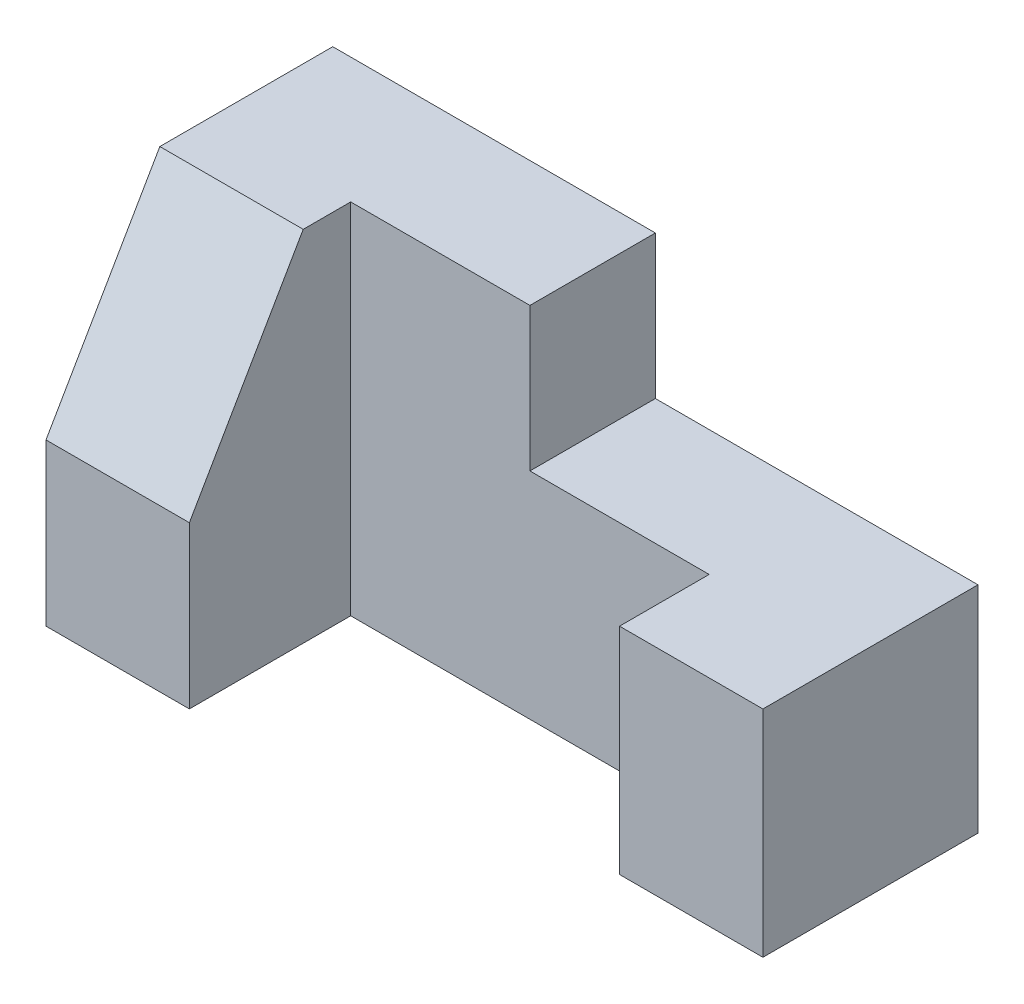
SolidWorks part; units mm, degrees
ref_plane "Front Plane" through (0, 0, 0) normal (0, 0, 1) x (1, 0, 0)
ref_plane "Top Plane" through (0, 0, 0) normal (0, 1, 0) x (1, 0, 0)
ref_plane "Right Plane" through (0, 0, 0) normal (1, 0, 0) x (0, 0, -1)
sketch "Sketch1" plane through (0, 0, 0) normal (0, 0, 1) x (1, 0, 0)
  line L0 (0, 0) -> (114.3, 0)
  line L1 (114.3, 0) -> (114.3, 38.1)
  line L2 (114.3, 38.1) -> (57.15, 38.1)
  line L3 (57.15, 38.1) -> (57.15, 63.5)
  line L4 (57.15, 63.5) -> (0, 63.5)
  line L5 (0, 63.5) -> (0, 0)
  line L6 (25.4, 63.5) -> (25.4, 0)
  line L7 (0, 28.575) -> (25.4, 28.575)
  line L8 (88.9, 38.1) -> (88.9, 0)
  dimension "D1" = 57.15
  dimension "D2" = 38.1
  dimension "D3" = 63.5
  dimension "D4" = 25.4
  dimension "D5" = 34.925
  dimension "D6" = 25.4
  dimension "D7" = 114.3
extrude "Boss-Extrude1" add sketch "Sketch1" along normal blind 22.225 contours L8 L2 L3 L4 L6 L0 region at (53.1813, 26.9875, 0)
extrude "Boss-Extrude2" add sketch "Sketch1<3>" along normal blind 38.1 contours L2 L8 L0 L1 region at (101.6, 19.05, 0)
sketch "Sketch1<3>" plane through (0, 0, 0) normal (0, 0, 1) x (1, 0, 0) same geometry as "Sketch1"
extrude "Boss-Extrude3" add sketch "Sketch1<4>" along normal blind 50.8 contours L7 L5 L0 L6 | L5 L7 L6 L4 region at (12.7, 14.2875, 0) region at (12.7, 46.0375, 0)
sketch "Sketch1<4>" plane through (0, 0, 0) normal (0, 0, 1) x (1, 0, 0) same geometry as "Sketch1"
sketch "Sketch2" plane through (0, 0, 0) normal (-1, 0, 0) x (0, 0, 1)
  line L0 (50.8, 28.575) -> (30.636, 63.5)
  line L1 (50.8, 63.5) -> (50.8, 0) construction
  line L2 (50.8, 63.5) -> (0, 63.5) construction
  line L3 (50.8, 28.575) -> (50.8, 63.5)
  line L4 (50.8, 63.5) -> (30.636, 63.5)
  dimension "D1" = 34.925
  dimension "D2" = 30
extrude "Cut-Extrude1" cut sketch "Sketch2" against normal blind 25.4
